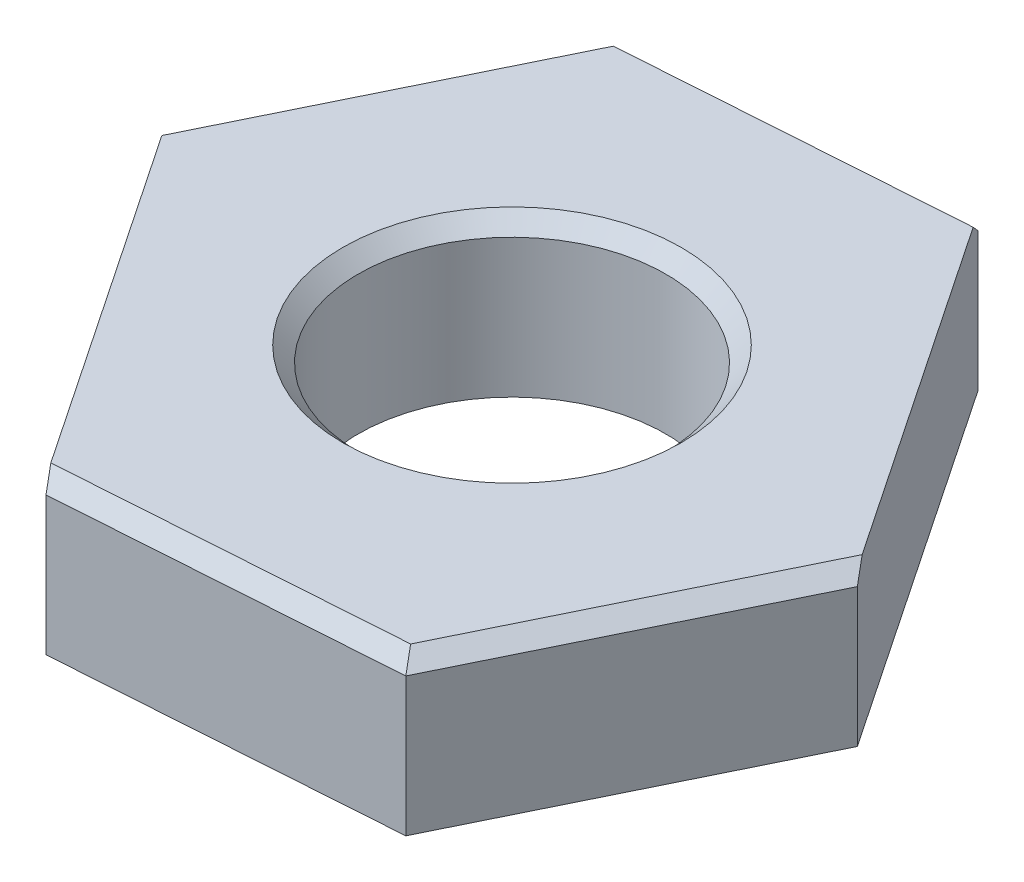
SolidWorks part; units mm, degrees
ref_plane "Front Plane" through (0, 0, 0) normal (0, 0, 1) x (1, 0, 0)
ref_plane "Top Plane" through (0, 0, 0) normal (0, 1, 0) x (1, 0, 0)
ref_plane "Right Plane" through (0, 0, 0) normal (1, 0, 0) x (0, 0, -1)
sketch "Sketch1" plane through (0, 0, 0) normal (0, 1, 0) x (1, 0, 0)
  line L1 (7.0886, -10.5397) -> (12.6719, 0.8691)
  line L2 (12.6719, 0.8691) -> (5.5833, 11.4088)
  line L3 (5.5833, 11.4088) -> (-7.0886, 10.5397)
  line L4 (-7.0886, 10.5397) -> (-12.6719, -0.8691)
  line L5 (-12.6719, -0.8691) -> (-5.5833, -11.4088)
  line L6 (-5.5833, -11.4088) -> (7.0886, -10.5397)
  circle A0 centre (0, 0) radius 11 construction
  circle A1 centre (0, 0) radius 5
extrude "Boss-Extrude1" add sketch "Sketch1" along normal blind 5
chamfer "Chamfer1" distance 0.5 angle 45 7 edges at (0, 5, 5) (-9.1276, 5, 6.1389) (-9.8803, 5, -4.8353) (-0.7527, 5, -10.9742) (9.1276, 5, -6.1389) (9.8803, 5, 4.8353) (0.7527, 5, 10.9742)
sketch "Sketch2" plane through (0, 5, 0) normal (0, 1, 0) x (1, 0, 0)
  line L0 (-12.3698, 1.3695) -> (-3.3134, -12.0959)
  line L1 (-12.0959, -0.8296) -> (-5.3295, -10.8902) construction
  line L2 (-12.3698, 1.3695) -> (-15.2781, -0.5865)
  line L3 (-15.2781, -0.5865) -> (-6.2217, -14.0519)
  line L4 (-6.2217, -14.0519) -> (-3.3134, -12.0959)
  line L5 (0, 0) -> (-8.8133, 13.104) construction
  line L6 (3.3961, 11.9731) -> (6.3043, 13.9291)
  line L7 (6.3043, 13.9291) -> (15.3607, 0.4637)
  line L8 (15.3607, 0.4637) -> (12.4524, -1.4923)
  line L9 (3.3961, 11.9731) -> (12.4524, -1.4923)
  dimension "D1" = 9.5
extrude "Cut-Extrude1" cut sketch "Sketch2" against normal through all
